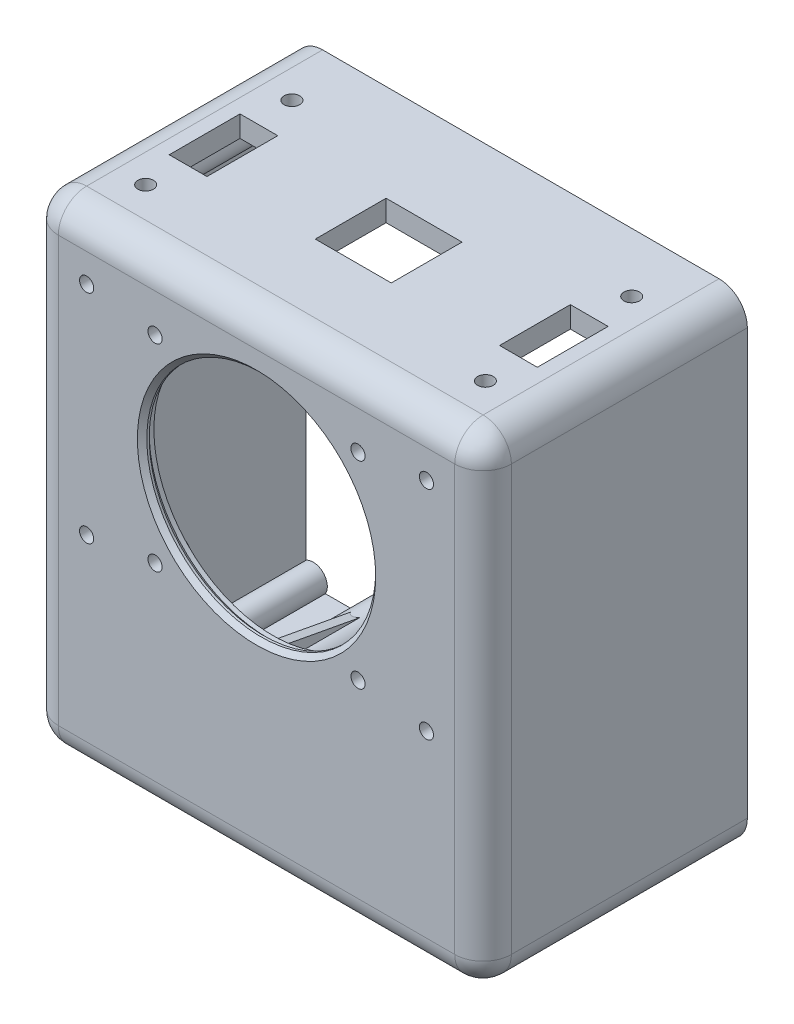
SolidWorks part; units mm, degrees
note: '?' marks a value the reader was unsure of.
material "PEI"
ref_plane "前视基准面" through (0, 0, 0) normal (0, 0, 1) x (1, 0, 0)
ref_plane "上视基准面" through (0, 0, 0) normal (0, 1, 0) x (1, 0, 0)
ref_plane "右视基准面" through (0, 0, 0) normal (1, 0, 0) x (0, 0, -1)
sketch "草图1" plane through (0, 0, 0) normal (0, 0, 1) x (1, 0, 0)
  line L1 (-48, 51) -> (48, 51)
  line L2 (-48, 51) -> (-48, -51)
  line L3 (-48, -51) -> (48, -51)
  line L4 (48, 51) -> (48, -51)
  line L5 (-48, 51) -> (48, -51) construction
  line L6 (-48, -51) -> (48, 51) construction
  point P0 (0, 0)
  dimension "D1" = 96
  dimension "D2" = 102
extrude "凸台-拉伸2" add sketch "草图1" against normal blind 62
fillet "圆角1" radius 6 12 edges at (48, -51, -31) (0, -51, -62) (-48, -51, -31) (0, -51, 0) (-48, 51, -31) (0, 51, -62) (48, 51, -31) (0, 51, 0) (48, 0, 0) (48, 0, -62) (-48, 0, 0) (-48, 0, -62)
shell "抽壳4" thickness 2.5
sketch "草图2" plane through (0, 0, 0) normal (0, 0, 1) x (1, 0, 0)
  line L0 (42, -51) -> (-42, -51) construction
  line L1 (0, 47.5285) -> (0, -40.1202) construction
  circle A0 centre (0, 16) radius 24.25
  dimension "D1" = 48.5
  dimension "D2" = 67
extrude "切除-拉伸1" cut sketch "草图2" against normal blind 10
chamfer "倒角1" distance 1 angle 45 1 edges at (24.25, 16, 0)
sketch "草图3" plane through (0, 0, 0) normal (0, 0, 1) x (1, 0, 0)
  line L0 (0, 16) -> (31.5574, 16) construction
  line L1 (0, 16) -> (0, 43.2952) construction
  circle A0 centre (21.5, 36.9225) radius 2.75
  circle A1 centre (21.5, -4.9225) radius 2.75
  circle A2 centre (-21.5, -4.9225) radius 2.75
  circle A3 centre (-21.5, 36.9225) radius 2.75
  dimension "D3" = 5.5
  dimension "D1" = 30
  dimension "D2" = 21.5
extrude "凸台-拉伸3" add sketch "草图3" against normal blind 5
sketch "草图4" plane through (0, 0, 0) normal (0, 0, 1) x (1, 0, 0)
  line L0 (0, 16) -> (36.4286, 16) construction
  line L1 (0, 16) -> (0, 35.5803) construction
  circle A1 centre (21.5, -4.9225) radius 1.5
  circle A8 centre (21.5, 36.9225) radius 1.5
  circle A9 centre (-21.5, -4.9225) radius 1.5
  circle A10 centre (-21.5, 36.9225) radius 1.5
  dimension "D2" = 3
extrude "切除-拉伸2" cut sketch "草图4" against normal blind 5.5
chamfer "倒角2" distance 1 angle 45 1 edges at (24.25, 16, -2.5)
ref_plane "基准面2" through (0, 0, -56) normal (0, 0, 1) x (1, 0, 0)
sketch "草图7" plane through (0, 0, -56) normal (0, 0, 1) x (1, 0, 0)
  line L1 (-54.5541, 53.0359) -> (54.5541, 53.0359)
  line L2 (-54.5541, 53.0359) -> (-54.5541, -53.0359)
  line L3 (-54.5541, -53.0359) -> (54.5541, -53.0359)
  line L4 (54.5541, 53.0359) -> (54.5541, -53.0359)
  line L5 (-54.5541, 53.0359) -> (54.5541, -53.0359) construction
  line L6 (-54.5541, -53.0359) -> (54.5541, 53.0359) construction
  point P0 (0, 0)
extrude "切除-拉伸3" cut sketch "草图7" against normal through all
ref_plane "基准面4" through (0, 0, -54) normal (0, 0, 1) x (1, 0, 0)
sketch "草图9" plane through (0, 0, -54) normal (0, 0, 1) x (1, 0, 0)
  line L2 (43.5, 45) -> (43.5, -45)
  line L3 (43.5, 45) -> (43.5, -45)
  line L13 (-42, 46.5) -> (42, 46.5)
  line L14 (-42, 46.5) -> (42, 46.5)
  line L16 (-43.5, 45) -> (-43.5, -45)
  line L17 (-43.5, 45) -> (-43.5, -45)
  line L18 (45.5, -45) -> (45.5, 45) construction
  line L19 (-42, -46.5) -> (42, -46.5)
  line L20 (-42, -46.5) -> (42, -46.5)
  line L21 (45.5, -45) -> (45.5, 45)
  line L23 (-45.5, 45) -> (-45.5, -45) construction
  line L24 (-45.5, 45) -> (-45.5, -45)
  line L25 (-42, -48.5) -> (42, -48.5) construction
  line L26 (-42, -48.5) -> (42, -48.5)
  line L27 (42, 48.5) -> (-42, 48.5) construction
  line L28 (42, 48.5) -> (-42, 48.5)
  arc A4 (43.5, 45) -> (42, 46.5) centre (42, 45) ccw
  arc A5 (43.5, 45) -> (42, 46.5) centre (42, 45) ccw
  arc A7 (-42, 46.5) -> (-43.5, 45) centre (-42, 45) ccw
  arc A8 (-42, 46.5) -> (-43.5, 45) centre (-42, 45) ccw
  arc A10 (-43.5, -45) -> (-42, -46.5) centre (-42, -45) ccw
  arc A11 (-43.5, -45) -> (-42, -46.5) centre (-42, -45) ccw
  arc A12 (45.5, 45) -> (42, 48.5) centre (42, 45) ccw construction
  arc A13 (42, -46.5) -> (43.5, -45) centre (42, -45) ccw
  arc A14 (42, -46.5) -> (43.5, -45) centre (42, -45) ccw
  arc A15 (45.5, 45) -> (42, 48.5) centre (42, 45) ccw
  arc A16 (-42, 48.5) -> (-45.5, 45) centre (-42, 45) ccw construction
  arc A17 (-42, 48.5) -> (-45.5, 45) centre (-42, 45) ccw
  arc A18 (-45.5, -45) -> (-42, -48.5) centre (-42, -45) ccw construction
  arc A19 (-45.5, -45) -> (-42, -48.5) centre (-42, -45) ccw
  arc A20 (42, -48.5) -> (45.5, -45) centre (42, -45) ccw construction
  arc A21 (42, -48.5) -> (45.5, -45) centre (42, -45) ccw
  dimension "D1" = 2
  dimension "D2" = 2
  dimension "D3" = 2
  dimension "D4" = 2
  dimension "D5" = 2
  dimension "D6" = 2
  dimension "D7" = 2
  dimension "D8" = 2
extrude "凸台-拉伸4" add sketch "草图9" along normal up to next
sketch "草图10" plane through (0, 0, -54) normal (0, 0, -1) x (-1, 0, 0)
  line L0 (-42, 46.5) -> (42, 46.5) construction
  line L1 (-43.5, -45) -> (-43.5, 45) construction
  line L2 (0, 0) -> (66.6227, 0) construction
  line L3 (0, 0) -> (0, 35.6239) construction
  line L4 (43.5, 45) -> (43.5, -45) construction
  line L5 (43.5, 45) -> (43.5, -45)
  line L6 (-42, 46.5) -> (42, 46.5)
  line L7 (-43.5, -45) -> (-43.5, 45) construction
  line L8 (-43.5, -45) -> (-43.5, 45)
  line L9 (42, -46.5) -> (-42, -46.5) construction
  line L10 (42, -46.5) -> (-42, -46.5)
  arc A0 (-39.4019, 46.5) -> (-43.5, 42.4019) centre (-42, 45) cw
  arc A1 (-39.4019, -46.5) -> (-43.5, -42.4019) centre (-42, -45) ccw
  arc A2 (39.4019, -46.5) -> (43.5, -42.4019) centre (42, -45) cw
  arc A3 (39.4019, 46.5) -> (43.5, 42.4019) centre (42, 45) ccw
  arc A4 (43.5, 45) -> (42, 46.5) centre (42, 45) ccw construction
  arc A5 (43.5, 45) -> (42, 46.5) centre (42, 45) ccw
  arc A6 (-42, 46.5) -> (-43.5, 45) centre (-42, 45) ccw construction
  arc A7 (-42, 46.5) -> (-43.5, 45) centre (-42, 45) ccw
  arc A8 (42, -46.5) -> (43.5, -45) centre (42, -45) ccw construction
  arc A9 (42, -46.5) -> (43.5, -45) centre (42, -45) ccw
  arc A10 (-43.5, -45) -> (-42, -46.5) centre (-42, -45) ccw construction
  arc A11 (-43.5, -45) -> (-42, -46.5) centre (-42, -45) ccw
  arc M3 (-43.5, 45) -> (-42, 46.5) centre (-42, 45) cw
  line M4 (-42, 46.5) -> (42, 46.5)
  arc M5 (42, 46.5) -> (43.5, 45) centre (42, 45) cw
  line M6 (43.5, 45) -> (43.5, -45)
  arc M7 (43.5, -45) -> (42, -46.5) centre (42, -45) cw
  line M8 (42, -46.5) -> (-42, -46.5)
  arc M9 (-42, -46.5) -> (-43.5, -45) centre (-42, -45) cw
  line M10 (-43.5, -45) -> (-43.5, 45)
  dimension "D1" = 3
extrude "凸台-拉伸5" add sketch "草图10" against normal up to next contours A0 L8 M4 M3 | A3 M4 M6 M5 | A2 L5 M8 M7 | L10 A1 M10 M9
sketch "草图12" plane through (0, 0, -2.5) normal (0, 0, -1) x (-1, 0, 0)
  line L0 (0, -36.4062) -> (0, 36.3744) construction
  circle A0 centre (0, -18) radius 4
  dimension "D1" = 8
  dimension "D2" = 18
extrude "凸台-拉伸6" add sketch "草图12" along normal up to surface (51.5 mm away) up to face at (0, 0, -54)
ref_axis "基准轴1" through (0, -18, -54) along (0, 0, 1)?
sketch "草图17" plane through (0, 0, 0) normal (1, 0, 0) x (0, 0, -1)
  line L0 (33.8128, -16.529) -> (2.5, -10.7101)
  line L1 (2.5, -22) -> (2.5, -9.25) construction
  line L2 (2.5, -10.7101) -> (2.5, -16.529)
  line L3 (2.5, -16.529) -> (33.8128, -16.529)
extrude "凸台-拉伸7" add sketch "草图17" along normal mid plane 2
pattern_circular "阵列(圆周)1" count 4 over 360 about axis through (0, -18, 0) along (0, 0, 1) of "凸台-拉伸7"
sketch "草图23" plane through (0, 0, -2.5) normal (0, 0, -1) x (-1, 0, 0)
  circle A1 centre (0, 16) radius 25.25 construction
  circle A2 centre (0, 16) radius 25.75
  circle A3 centre (0, 16) radius 25.75
  circle A4 centre (0, 16) radius 25.25
  dimension "D1" = 0.5
sketch "草图19" plane through (0, 0, -54) normal (0, 0, -1) x (-1, 0, 0)
  line L0 (0, 0) -> (56.4128, 0) construction
  line L1 (0, 0) -> (0, 27.5595) construction
  circle A0 centre (-42, -45) radius 1.65
  circle A1 centre (42, -45) radius 1.65
  circle A2 centre (42, 45) radius 1.65
  circle A3 centre (-42, 45) radius 1.65
  circle A4 centre (0, -18) radius 1.65
  dimension "D1" = 3.3
  dimension "D2" = 3.3
extrude "切除-拉伸4" cut sketch "草图19" against normal blind 10
sketch "草图20" plane through (0, 0, -2.5) normal (0, 0, -1) x (-1, 0, 0)
  line L0 (0, 16) -> (38.3651, 16) construction
  line L1 (0, 16) -> (0, 25.9964) construction
  circle A0 centre (36, 39) radius 2.5
  circle A1 centre (36, -7) radius 2.5
  circle A2 centre (-36, 39) radius 2.5
  circle A3 centre (-36, -7) radius 2.5
  dimension "D3" = 5
  dimension "D1" = 23
  dimension "D2" = 36
extrude "凸台-拉伸8" add sketch "草图20" along normal blind 1
hole_wizard "打孔尺寸开槽半沉头螺钉的类型2" positions "3D草图2" profile "草图22" countersink size "M2" standard "GB" end condition through all
sketch3d "3D草图2"
  line L0 (36, 39, -3.5) -> (36, 39, -2.5) construction
  line L1 (-36, 39, -3.5) -> (-36, 39, -2.5) construction
  line L2 (-36, -7, -3.5) -> (-36, -7, -2.5) construction
  line L3 (36, -7, -3.5) -> (36, -7, -2.5) construction
  point P0 (36, 39, -3.5)
  point P4 (-36, 39, -3.5)
  point P8 (-36, -7, -3.5)
  point P12 (36, -7, -3.5)
sketch "草图22" plane through (36, 39, -3.5) normal (1, 0, 0) x (0, 1, 0)
  line L0 (0, 0) -> (0, 3.5)
  line L1 (0, 3.5) -> (1.5, 3.5)
  line L2 (1.5, 3.5) -> (1.5, 0.55)
  line L3 (1.5, 0.55) -> (2.05, 0)
  line L5 (2.05, 0) -> (0, 0)
  line L6 (-1.5, 0.55) -> (-2.05, 0) construction
  line L11 (0, -6.35) -> (0, 107.95) construction
  dimension "通孔孔直径" = 3
  dimension "通孔孔深度" = 3.5
  dimension "近端锥形沉头孔直径" = 4.1
  dimension "近端锥形沉头孔角度" = 90
extrude "凸台-拉伸10" add sketch "草图23" along normal blind 1
sketch "草图25" plane through (0, 46.5, 0) normal (0, -1, 0) x (1, 0, 0)
  line L0 (0, 0) -> (0, -56) construction
  line L1 (42, -56) -> (-42, -56) construction
  line L2 (0, -28) -> (37.5215, -28) construction
  circle A0 centre (36, -43.5) radius 2.9621
  circle A1 centre (36, -12.5) radius 2.9621
  circle A2 centre (-36, -43.5) radius 2.9621
  circle A3 centre (-36, -12.5) radius 2.9621
  dimension "D1" = 15.5
  dimension "D2" = 36
extrude "凸台-拉伸11" add sketch "草图25" along normal blind 2
hole_wizard "打孔尺寸开槽半沉头螺钉的类型3" positions "3D草图3" profile "草图26" countersink size "M3" standard "GB"
sketch3d "3D草图3"
  line L0 (36, 44.5, -43.5) -> (36, 46.5, -43.5) construction
  line L1 (36, 44.5, -12.5) -> (36, 46.5, -12.5) construction
  line L2 (-36, 44.5, -43.5) -> (-36, 46.5, -43.5) construction
  line L3 (-36, 44.5, -12.5) -> (-36, 46.5, -12.5) construction
  point P0 (36, 44.5, -43.5)
  point P4 (36, 44.5, -12.5)
  point P8 (-36, 44.5, -43.5)
  point P12 (-36, 44.5, -12.5)
sketch "草图26" plane through (36, 44.5, -43.5) normal (1, 0, 0) x (0, 0, -1)
  line L0 (0, 0) -> (0, 15.9914)
  line L1 (0, 15.9914) -> (1.65, 15)
  line L2 (1.65, 15) -> (1.65, 1.15)
  line L3 (1.65, 1.15) -> (2.8, 0)
  line L5 (2.8, 0) -> (0, 0)
  line L6 (-1.65, 1.15) -> (-2.8, 0) construction
  line L10 (0, 15.9914) -> (-1.65, 15) construction
  line L11 (0, -6.35) -> (0, 107.95) construction
  dimension "孔直径" = 3.3
  dimension "孔深度" = 15
  dimension "近端锥形沉头孔直径" = 5.6
  dimension "近端锥形沉头孔角度" = 90
  dimension "导头角度" = 118
sketch "草图27" plane through (0, 51, 0) normal (0, 1, 0) x (1, 0, 0)
  line L0 (0, 0) -> (0, 56) construction
  line L1 (42, 56) -> (-42, 56) construction
  line L2 (0, 28) -> (-41.0396, 28) construction
  line L3 (39, 35.5) -> (31, 35.5)
  line L4 (-39, 35.5) -> (-31, 35.5)
  line L5 (-39, 35.5) -> (-39, 20.5)
  line L6 (-39, 20.5) -> (-31, 20.5)
  line L7 (-31, 35.5) -> (-31, 20.5)
  line L8 (-39, 35.5) -> (-31, 20.5) construction
  line L9 (-39, 20.5) -> (-31, 35.5) construction
  line L10 (39, 35.5) -> (39, 20.5)
  line L11 (39, 20.5) -> (31, 20.5)
  line L12 (31, 35.5) -> (31, 20.5)
  line L14 (-8.05, 35.5) -> (8.05, 35.5)
  line L15 (-8.05, 35.5) -> (-8.05, 20.5)
  line L16 (-8.05, 20.5) -> (8.05, 20.5)
  line L17 (8.05, 35.5) -> (8.05, 20.5)
  line L18 (-8.05, 35.5) -> (8.05, 20.5) construction
  line L19 (-8.05, 20.5) -> (8.05, 35.5) construction
  point P3 (-35, 28)
  dimension "D1" = 8
  dimension "D2" = 15
  dimension "D3" = 35
  dimension "D4" = 16.1
  dimension "D5" = 15
extrude "切除-拉伸5" cut sketch "草图27" against normal up to next
